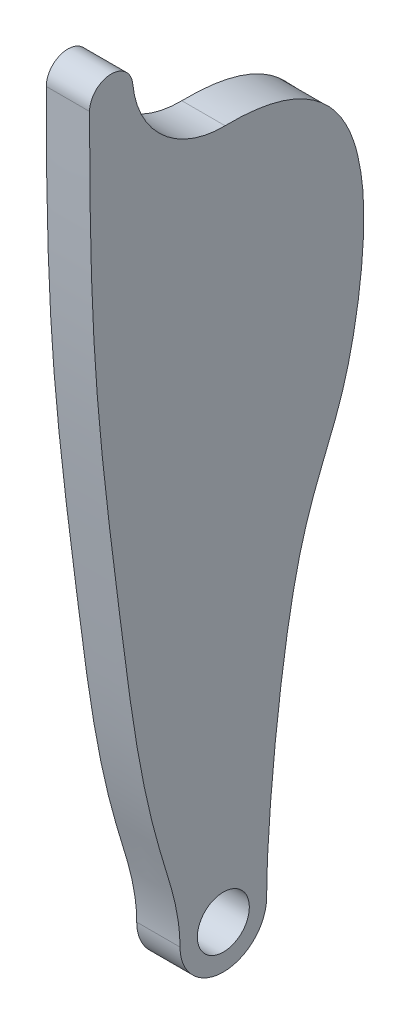
SolidWorks part; units mm, degrees
ref_plane "Front Plane" through (0, 0, 0) normal (0, 0, 1) x (1, 0, 0)
ref_plane "Top Plane" through (0, 0, 0) normal (0, 1, 0) x (1, 0, 0)
ref_plane "Right Plane" through (0, 0, 0) normal (1, 0, 0) x (0, 0, -1)
sketch "Sketch1" plane through (0, 0, 0) normal (1, 0, 0) x (0, 0, -1)
  line L0 (0, 0) -> (0, -180) construction
  line L3 (-10, -180) -> (10, -180) construction
  line L4 (-30.8795, -2.5) -> (-25.8795, -2.5) construction
  line L5 (21.2368, -15) -> (26.2368, -15) construction
  arc A1 (-20.9027, -2.0192) -> (-30.8795, -2.5) centre (-25.8795, -2.5) ccw
  circle A2 centre (0, -180) radius 6
  arc A3 (10, -180) -> (-10, -180) centre (0, -180) cw
  arc A4 (-20.9027, -2.0192) -> (17.1528, -12.1154) centre (0, 0) ccw
  arc A5 (17.1528, -12.1154) -> (26.2368, -15) centre (21.2368, -15) cw
  spline S0 degree 3 poles (-30.8795, -2.5) (-30.8795, -21.7138) (-30.3975, -56.7184) (-23.6238, -108.9459) (-18.3314, -149.9703) (-10, -172.3405) (-10, -180) knots 0 0 0 0 0.308445 0.60419 0.874788 1 1 1 1
  spline S1 degree 3 poles (26.2368, -15) (26.2368, -30.8457) (35.4595, -43.5625) (29.1579, -90.4294) (15.335, -110.8403) (10, -165.4565) (10, -180) knots 0 0 0 0 0.18761 0.382215 0.559767 0.781851 0.781851 0.781851 0.781851
  point P14 (17.1528, -117.3818)
  point P16 (-29.2937, -57.7324)
  point P19 (-23.443, -110.3884)
  point P21 (31.8122, -23.9167)
  point P23 (38.0942, -48.7713)
  point P24 (27.4422, -91.9254)
  point P25 (19.9312, -124.9738)
  point P26 (29.9003, -19.0004)
  point P27 (0, 0)
  point P28 (34.8166, -51.5025)
  point P29 (25.8034, -94.2469)
  point P30 (17.473, -125.52)
  point P31 (0, 0)
  point P32 (20.8798, -6.9307)
  point P33 (-21.8367, -2.6752)
  point P34 (0, 0)
  point P35 (29.6113, -35.9008)
  point P36 (33.4144, -54.1158)
  point P37 (27.7444, -86.8325)
  point P38 (32.032, -47.976)
  point P39 (12, -180)
  point P40 (0, 0)
  dimension "D2" = 12
  dimension "D3" = 10
  dimension "D4" = 5
  dimension "D5" = 21
  dimension "D1" = 180
  dimension "D6" = 2.5
  dimension "D7" = 15
extrude "Boss-Extrude1" add sketch "Sketch1" along normal blind 10 contours S1 A5 A4 A1 S0 A3 A2 region at (0, -82.7198, 1.0602)
sketch "Sketch2" plane through (10, 0, 0) normal (1, 0, 0) x (0, 0, -1)
  arc A0 (-20.9027, -2.0192) -> (17.1528, -12.1154) centre (0, 0) ccw construction
  arc A1 (26.2368, -15) -> (17.1528, -12.1154) centre (21.2368, -15) ccw construction
  arc A2 (26.2368, -15) -> (17.1528, -12.1154) centre (21.2368, -15) ccw
  arc A3 (0.4071, -20.9961) -> (17.1528, -12.1154) centre (0, 0) ccw
  spline S0 degree 3 poles (0.4071, -20.9961) (17.3876, -20.6668) (27.719, -27.8698) (31.0225, -42.2314) knots 0 0 0 0 1 1 1 1
  spline S1 degree 3 poles (422.4147, 903.163) (-36.2876, -38.5795) (42.231, 6.7979) (29.1579, -90.4294) (0.2083, -133.1765) (3.1256, -451.473) (129.9842, 812.7596) knots -0.601491 -0.601491 -0.601491 -0.601491 0.18761 0.382215 0.559767 1.432148 1.432148 1.432148 1.432148 only from (26.2368, -15) to (10, -180) construction
  spline S2 degree 3 poles (26.2368, -15) (26.2368, -27.8659) (29.2212, -34.4004) (31.0225, -42.2314) knots 0 0 0 0 0.152329 0.152329 0.152329 0.152329
  point P2 (25.707, -30.6805)
extrude "Cut-Extrude1" cut sketch "Sketch2" against normal through all both and the other way through all
